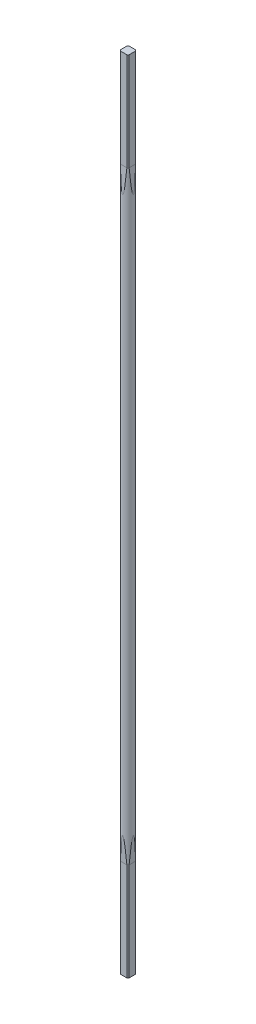
SolidWorks part; units mm, degrees
ref_plane "Front Plane" through (0, 0, 0) normal (0, 0, 1) x (1, 0, 0)
ref_plane "Top Plane" through (0, 0, 0) normal (0, 1, 0) x (1, 0, 0)
ref_plane "Right Plane" through (0, 0, 0) normal (1, 0, 0) x (0, 0, -1)
sketch "Sketch1" plane through (0, 0, 0) normal (0, 1, 0) x (1, 0, 0)
  circle A0 centre (0, 0) radius 3.3
  dimension "D1" = 6.6
extrude "Boss-Extrude1" add sketch "Sketch1" along normal blind 245 and the other way blind 245
sketch "Sketch2" plane through (0, 245, 0) normal (0, 1, 0) x (1, 0, 0)
  line L1 (-2.65, 2.65) -> (2.65, 2.65)
  line L2 (-2.65, 2.65) -> (-2.65, -2.65)
  line L3 (-2.65, -2.65) -> (2.65, -2.65)
  line L4 (2.65, 2.65) -> (2.65, -2.65)
  dimension "D1" = 5.3
  dimension "D2" = 5.3
  dimension "D3" = 2.65
  dimension "D4" = 2.65
extrude "Cut-Extrude1" cut sketch "Sketch2" against normal blind 60 flip side to cut
sketch "Sketch3" plane through (0, 185, 0) normal (0, 1, 0) x (1, 0, 0)
  line L1 (-1.9666, -2.65) -> (1.9666, -2.65) construction
  line L2 (2.65, -1.9666) -> (2.65, 1.9666) construction
  line L3 (1.9666, 2.65) -> (-1.9666, 2.65) construction
  line L4 (-2.65, 1.9666) -> (-2.65, -1.9666) construction
  line L5 (-1.9666, -2.65) -> (1.9666, -2.65)
  line L6 (2.65, -1.9666) -> (2.65, 1.9666)
  line L7 (1.9666, 2.65) -> (-1.9666, 2.65)
  line L8 (-2.65, 1.9666) -> (-2.65, -1.9666)
  line L9 (-2.65, 1.9666) -> (-2.65, 2.65)
  line L10 (-2.65, 2.65) -> (-1.9666, 2.65)
  line L11 (1.9666, 2.65) -> (2.65, 2.65)
  line L12 (2.65, 2.65) -> (2.65, 1.9666)
  line L13 (2.65, -1.9666) -> (2.65, -2.65)
  line L14 (2.65, -2.65) -> (1.9666, -2.65)
  line L15 (-1.9666, -2.65) -> (-2.65, -2.65)
  line L16 (-2.65, -2.65) -> (-2.65, -1.9666)
extrude "Cut-Extrude2" cut sketch "Sketch3" against normal blind 15 draft 2.5 flip side to cut
sketch "Sketch4" plane through (0, -245, 0) normal (0, -1, 0) x (1, 0, 0)
  line L1 (-2.65, 2.65) -> (2.65, 2.65)
  line L2 (-2.65, 2.65) -> (-2.65, -2.65)
  line L3 (-2.65, -2.65) -> (2.65, -2.65)
  line L4 (2.65, 2.65) -> (2.65, -2.65)
  dimension "D1" = 5.3
  dimension "D2" = 5.3
  dimension "D3" = 2.65
  dimension "D4" = 2.65
extrude "Cut-Extrude3" cut sketch "Sketch4" against normal blind 60 flip side to cut
sketch "Sketch5" plane through (0, -185, 0) normal (0, -1, 0) x (1, 0, 0)
  line L0 (1.9666, -2.65) -> (-1.9666, -2.65) construction
  line L1 (2.65, 1.9666) -> (2.65, -1.9666) construction
  line L2 (-1.9666, 2.65) -> (1.9666, 2.65) construction
  line L3 (-2.65, -1.9666) -> (-2.65, 1.9666) construction
  line L4 (1.9666, -2.65) -> (-1.9666, -2.65)
  line L5 (2.65, 1.9666) -> (2.65, -1.9666)
  line L6 (-1.9666, 2.65) -> (1.9666, 2.65)
  line L7 (-2.65, -1.9666) -> (-2.65, 1.9666)
  line L8 (-2.65, -1.9666) -> (-2.65, -2.65)
  line L9 (-2.65, -2.65) -> (-1.9666, -2.65)
  line L10 (1.9666, -2.65) -> (2.65, -2.65)
  line L11 (2.65, -2.65) -> (2.65, -1.9666)
  line L12 (2.65, 1.9666) -> (2.65, 2.65)
  line L13 (2.65, 2.65) -> (1.9666, 2.65)
  line L14 (-1.9666, 2.65) -> (-2.65, 2.65)
  line L15 (-2.65, 2.65) -> (-2.65, 1.9666)
extrude "Cut-Extrude4" cut sketch "Sketch5" against normal blind 15 draft 2.5 flip side to cut
sketch "Sketch6" plane through (0, -245, 0) normal (0, -1, 0) x (1, 0, 0)
  circle A0 centre (0, 0) radius 3.3
curve "Helix/Spiral1" pitch 8 height 490 turns 61.25
ref_plane "Plane1" through (0, -245, -3.3) normal (0.933, 0.36, 0) x (0, 0, -1)
